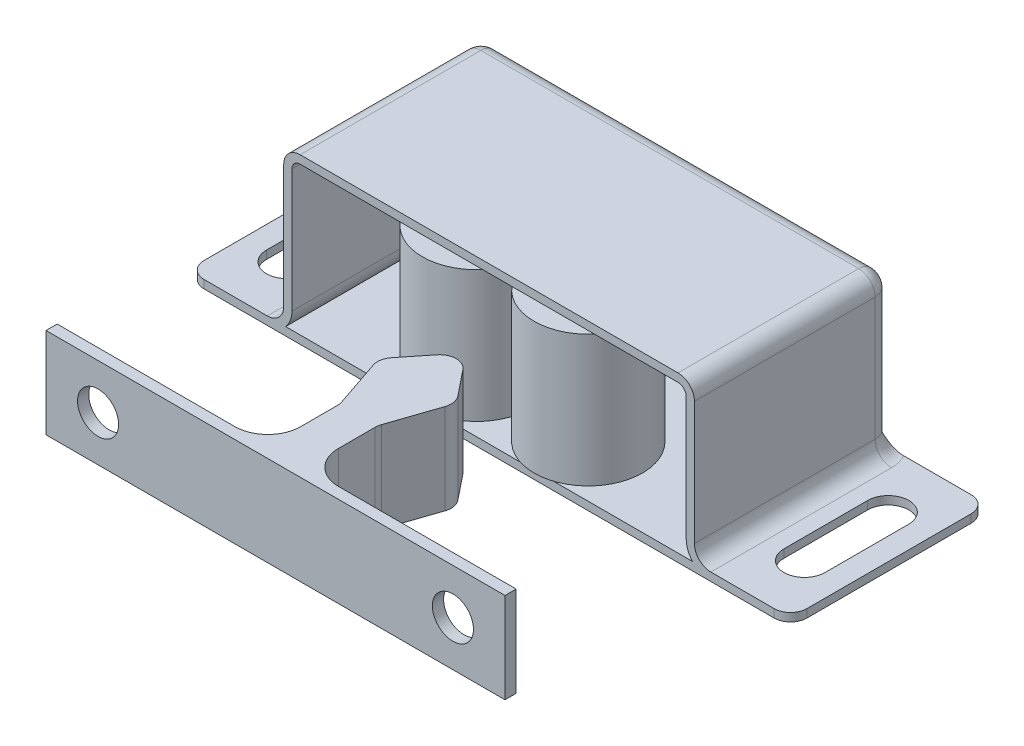
SolidWorks part; units mm, degrees
ref_plane "Front" through (0, 0, 0) normal (0, 0, 1) x (1, 0, 0)
ref_plane "Top" through (0, 0, 0) normal (0, 1, 0) x (1, 0, 0)
ref_plane "Right" through (0, 0, 0) normal (1, 0, 0) x (0, 0, -1)
sketch "Sketch2" plane through (0, 0, 0) normal (0, 0, 1) x (1, 0, 0)
  line L0 (15.875, -6.0325) -> (23.3045, -6.0325)
  line L1 (-15.875, 6.0325) -> (15.875, 6.0325)
  line L2 (-15.875, 6.0325) -> (-15.875, -6.0325)
  line L3 (-15.875, -6.0325) -> (15.875, -6.0325) construction
  line L4 (15.875, 6.0325) -> (15.875, -6.0325)
  line L5 (-15.875, 6.0325) -> (15.875, -6.0325) construction
  line L6 (-15.875, -6.0325) -> (15.875, 6.0325) construction
  line L7 (23.3045, -6.0325) -> (23.3045, -6.6675)
  line L8 (23.3045, -6.6675) -> (-23.3045, -6.6675)
  line L9 (-23.3045, -6.6675) -> (-23.3045, -6.0325)
  line L10 (-23.3045, -6.0325) -> (-15.875, -6.0325)
  point P0 (0, 0)
  dimension "D1" = 12.065
  dimension "D2" = 31.75
  dimension "D3" = 12.7
  dimension "D4" = 46.609
extrude "Boss-Extrude1" add sketch "Sketch2" along normal blind 15.24
fillet "Fillet1" radius 1.27 4 edges at (-23.3045, -6.35, 0) (-23.3045, -6.35, 15.24) (23.3045, -6.35, 0) (23.3045, -6.35, 15.24)
fillet "Fillet3" radius 1.27 5 edges at (0, 6.0325, 0) (15.875, 6.0325, 7.62) (-15.875, 6.0325, 7.62) (15.875, 0, 0) (-15.875, 0, 0)
fillet "Fillet2" radius 1.27 4 edges at (-15.875, -6.0325, 8.255) (15.875, -6.0325, 8.255) (-15.503, -6.0325, 0.372) (15.503, -6.0325, 0.372)
sketch "Sketch3" plane through (0, -6.0325, 0) normal (0, 1, 0) x (1, 0, 0)
  line L0 (0, 0) -> (0, -15.24) construction
  line L1 (14.605, -15.24) -> (-14.605, -15.24) construction
  line L2 (-20.0025, -7.62) -> (20.0025, -7.62) construction
  line L3 (-20.0025, -4.3815) -> (-20.0025, -10.8585) construction
  line L4 (-18.415, -4.3815) -> (-18.415, -10.8585)
  line L5 (-21.59, -4.3815) -> (-21.59, -10.8585)
  line L6 (20.0025, -4.3815) -> (20.0025, -10.8585) construction
  line L7 (21.59, -4.3815) -> (21.59, -10.8585)
  line L8 (18.415, -4.3815) -> (18.415, -10.8585)
  line L9 (-20.0025, -2.794) -> (-20.0025, -12.446) construction
  arc A0 (-18.415, -4.3815) -> (-21.59, -4.3815) centre (-20.0025, -4.3815) ccw
  arc A1 (-21.59, -10.8585) -> (-18.415, -10.8585) centre (-20.0025, -10.8585) ccw
  arc A2 (21.59, -4.3815) -> (18.415, -4.3815) centre (20.0025, -4.3815) ccw
  arc A3 (18.415, -10.8585) -> (21.59, -10.8585) centre (20.0025, -10.8585) ccw
  point P7 (0, -7.62)
  point P10 (-20.0025, -7.62)
  point P15 (20.0025, -7.62)
  dimension "D1" = 40.005
  dimension "D2" = 3.175
  dimension "D3" = 9.652
extrude "Cut-Extrude1" cut sketch "Sketch3" against normal through all
sketch "Sketch4" plane through (0, 6.0325, 0) normal (0, 1, 0) x (1, 0, 0)
  line L0 (0, 0) -> (0, -15.24) construction
  line L1 (14.605, -15.24) -> (-14.605, -15.24) construction
  line L2 (-4.318, -11.8872) -> (4.318, -11.8872) construction
  circle A0 centre (-4.318, -11.8872) radius 4.191
  circle A1 centre (4.318, -11.8872) radius 4.191
  point P7 (0, -11.8872)
  dimension "D1" = 8.382
  dimension "D2" = 3.3528
  dimension "D3" = 8.636
extrude "Boss-Extrude2" add sketch "Sketch4" against normal offset from surface (10.16 mm away) 1.27 from offset 1.27 separate body up to face at (-20.0025, -6.6675, 7.62) offset against normal yes
shell "Shell1" thickness 0.635 removed face at (0, -2.1167, 15.24)
fillet "Fillet6" radius 1.27 1 edges at (0, -6.0325, 0.635)
sketch "Sketch5" plane through (0, -6.0325, 0) normal (0, 1, 0) x (1, 0, 0)
  line L0 (0, 0) -> (0, -31.75) construction
  line L1 (-1.4605, -30.8864) -> (-1.4605, -25.2984)
  line L2 (-17.7419, -30.8864) -> (-1.4605, -30.8864)
  line L3 (-17.7419, -30.8864) -> (-17.7419, -31.75)
  line L4 (-17.7419, -31.75) -> (17.7419, -31.75)
  line L5 (17.7419, -30.8864) -> (17.7419, -31.75)
  line L6 (-1.4605, -25.2984) -> (-2.9972, -20.7584)
  line L7 (-2.9972, -20.7584) -> (0, -17.018)
  line L8 (1.4605, -30.8864) -> (1.4605, -25.2984)
  line L9 (2.9972, -20.7584) -> (0, -17.018)
  line L10 (1.4605, -25.2984) -> (2.9972, -20.7584)
  line L11 (1.4605, -30.8864) -> (17.7419, -30.8864)
  dimension "D1" = 0.8636
  dimension "D2" = 35.4838
  dimension "D3" = 14.732
  dimension "D4" = 5.588
  dimension "D5" = 2.921
  dimension "D6" = 5.9944
  dimension "D7" = 31.75
extrude "Boss-Extrude3" add sketch "Sketch5" along normal blind 6.985 separate body
fillet "Fillet7" radius 2.54 2 edges at (-1.4605, -2.54, 30.8864) (1.4605, -2.54, 30.8864)
fillet "Fillet8" radius 1.27 5 edges at (1.4605, -2.54, 25.2984) (2.9972, -2.54, 20.7584) (0, -2.54, 17.018) (-2.9972, -2.54, 20.7584) (-1.4605, -2.54, 25.2984)
sketch "Sketch6" plane through (0, 0, 31.75) normal (0, 0, 1) x (1, 0, 0)
  line L0 (0, -6.0325) -> (0, 0.9525) construction
  line L1 (-15.7251, -6.0325) -> (15.7251, -6.0325) construction
  line L2 (-17.7419, 0.9525) -> (17.7419, 0.9525) construction
  line L3 (0, -2.54) -> (-13.716, -2.54) construction
  line L4 (0, -2.54) -> (13.716, -2.54) construction
  circle A0 centre (-13.716, -2.54) radius 1.5875
  circle A1 centre (13.716, -2.54) radius 1.5875
  dimension "D2" = 3.175
  dimension "D1" = 27.432
extrude "Cut-Extrude2" cut sketch "Sketch6" against normal through all
